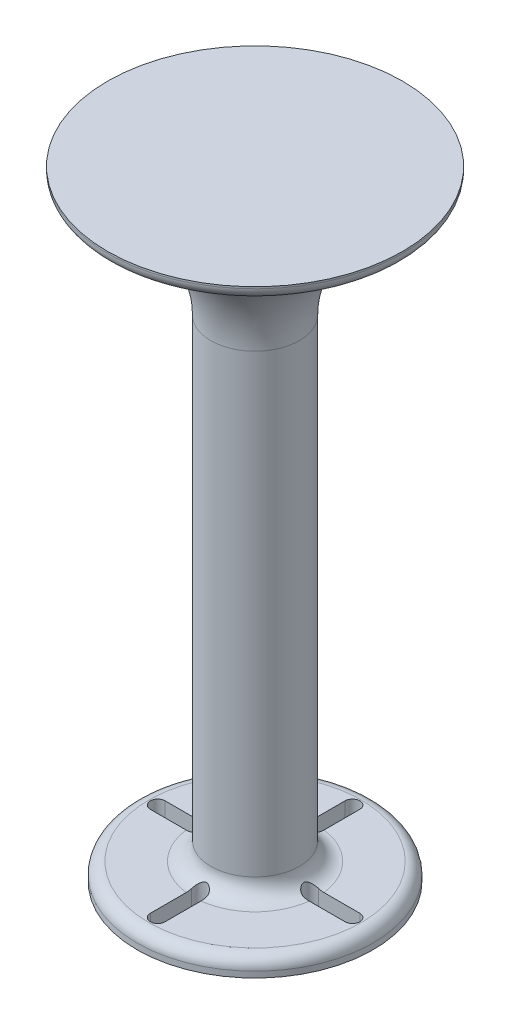
SolidWorks part; units mm, degrees
ref_plane "Front Plane" through (0, 0, 0) normal (0, 0, 1) x (1, 0, 0)
ref_plane "Top Plane" through (0, 0, 0) normal (0, 1, 0) x (1, 0, 0)
ref_plane "Right Plane" through (0, 0, 0) normal (1, 0, 0) x (0, 0, -1)
sketch "Sketch1" plane through (0, 0, 0) normal (0, 1, 0) x (1, 0, 0)
  circle A0 centre (0, 0) radius 20
  dimension "D1" = 40
extrude "Boss-Extrude1" add sketch "Sketch1" along normal blind 3
sketch "Sketch2" plane through (0, 3, 0) normal (0, 1, 0) x (1, 0, 0)
  circle A0 centre (0, 0) radius 7.5
  dimension "D1" = 15
extrude "Boss-Extrude2" add sketch "Sketch2" along normal blind 100
sketch "Sketch3" plane through (0, 103, 0) normal (0, 1, 0) x (1, 0, 0)
  circle A0 centre (0, 0) radius 25
  dimension "D1" = 50
extrude "Boss-Extrude3" add sketch "Sketch3" along normal blind 2
fillet "Fillet3" radius 20 1 edges at (0, 103, 7.5)
fillet "Fillet4" radius 2 1 edges at (0, 103, 25)
fillet "Fillet6" radius 3 1 edges at (0, 3, 7.5)
sketch "Sketch4" plane through (0, 0, 0) normal (0, -1, 0) x (1, 0, 0)
  line L0 (-20, 0) -> (20, 0) construction
  line L1 (0, -20) -> (0, 20) construction
  line L2 (0, -16.5) -> (0, -9.5) construction
  line L3 (-1.25, -16.5) -> (-1.25, -9.5)
  line L4 (1.25, -16.5) -> (1.25, -9.5)
  line L5 (-16.5, 0) -> (-9.5, 0) construction
  line L6 (-16.5, 1.25) -> (-9.5, 1.25)
  line L7 (-16.5, -1.25) -> (-9.5, -1.25)
  line L8 (0, 16.5) -> (0, 9.5) construction
  line L9 (1.25, 16.5) -> (1.25, 9.5)
  line L10 (-1.25, 16.5) -> (-1.25, 9.5)
  line L11 (16.5, 0) -> (9.5, 0) construction
  line L12 (16.5, -1.25) -> (9.5, -1.25)
  line L13 (16.5, 1.25) -> (9.5, 1.25)
  circle A0 centre (0, 0) radius 20 construction
  circle A1 centre (0, 0) radius 8 construction
  circle A2 centre (0, 0) radius 13 construction
  arc A3 (-1.25, -16.5) -> (1.25, -16.5) centre (0, -16.5) ccw
  arc A4 (1.25, -9.5) -> (-1.25, -9.5) centre (0, -9.5) ccw
  arc A5 (-16.5, 1.25) -> (-16.5, -1.25) centre (-16.5, 0) ccw
  arc A6 (-9.5, -1.25) -> (-9.5, 1.25) centre (-9.5, 0) ccw
  arc A7 (1.25, 16.5) -> (-1.25, 16.5) centre (0, 16.5) ccw
  arc A8 (-1.25, 9.5) -> (1.25, 9.5) centre (0, 9.5) ccw
  arc A9 (16.5, -1.25) -> (16.5, 1.25) centre (16.5, 0) ccw
  arc A10 (9.5, 1.25) -> (9.5, -1.25) centre (9.5, 0) ccw
  point P7 (0, 0)
  point P11 (0, 0)
  point P12 (-13, 0)
  point P13 (0, -13)
  point P14 (13, 0)
  point P15 (0, 13)
  point P18 (0, -13)
  point P23 (-17.5858, -2.6735)
  point P24 (0, 0)
  point P28 (-13, 0)
  point P35 (0, 13)
  point P42 (13, 0)
  dimension "D1" = 16
  dimension "D2" = 26
  dimension "D3" = 2.5
  dimension "D4" = 9.5
  dimension "D5" = 4
extrude "Cut-Extrude1" cut sketch "Sketch4" against normal up to next
fillet "Fillet8" radius 2 1 edges at (0, 3, 20)
